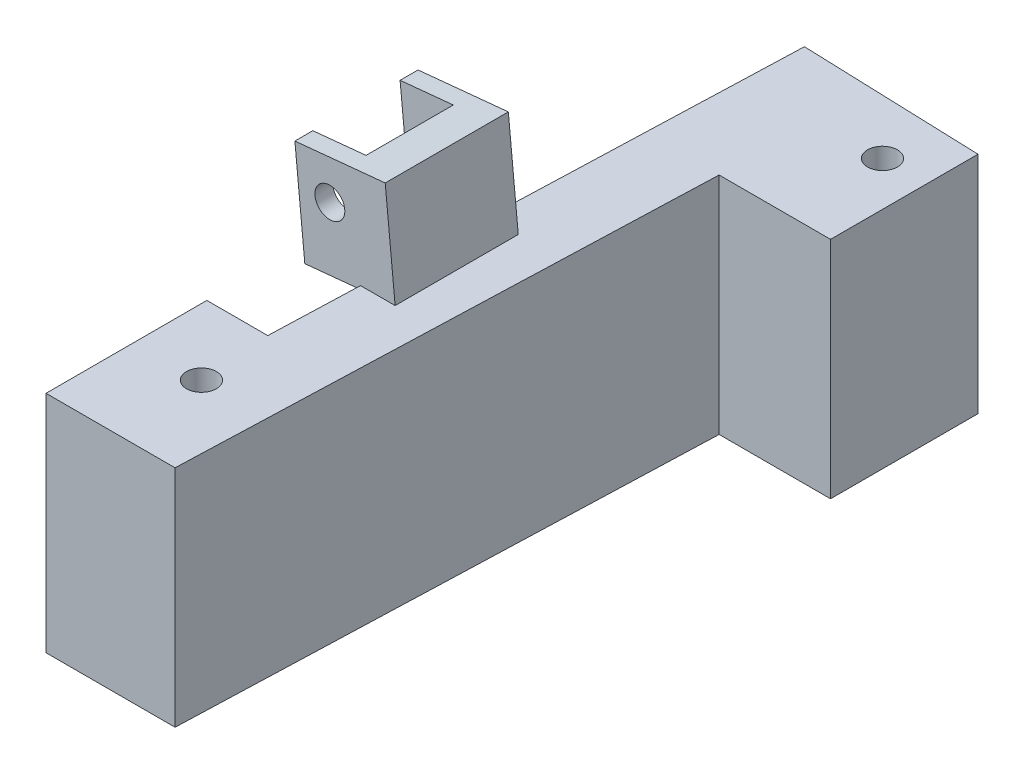
SolidWorks part; units mm, degrees
ref_plane "Front Plane" through (0, 0, 0) normal (0, 0, 1) x (1, 0, 0)
ref_plane "Top Plane" through (0, 0, 0) normal (0, 1, 0) x (1, 0, 0)
ref_plane "Right Plane" through (0, 0, 0) normal (1, 0, 0) x (0, 0, -1)
sketch "Sketch1" plane through (0, 0, 0) normal (0, 0, 1) x (1, 0, 0)
  line L0 (476.9237, 158.5913) -> (479.0335, 137.0791)
  line L1 (479.0335, 137.0791) -> (498.2247, 138.9613)
  line L2 (498.2247, 138.9613) -> (496.115, 160.4735)
  line L3 (496.115, 160.4735) -> (476.9237, 158.5913)
  line L4 (485.2846, 141.5205) -> (469.8952, 140.0112) construction
  line L5 (485.2846, 141.5205) -> (469.8952, 140.0112)
  arc A0 (489.9044, 158.7414) -> (483.4252, 160.4795) centre (484.3549, 151) ccw construction
  arc A1 (491.3026, 144.4842) -> (489.9044, 158.7414) centre (484.3549, 151) ccw construction
  arc A2 (485.2846, 141.5205) -> (491.3026, 144.4842) centre (484.3549, 151) ccw construction
  arc A3 (489.9044, 158.7414) -> (483.4252, 160.4795) centre (484.3549, 151) ccw
  arc A4 (491.3026, 144.4842) -> (489.9044, 158.7414) centre (484.3549, 151) ccw
  arc A5 (485.2846, 141.5205) -> (491.3026, 144.4842) centre (484.3549, 151) ccw
  dimension "D1" = 6.35
  dimension "D2" = 3.81
extrude "Boss-Extrude5" add sketch "Sketch1" against normal blind 22.352 contours A5 L5 L0 L1 L2 L3 A3 A4 region at (482.0029, 140.8922, 0)
sketch "Sketch2" plane through (0, 0, -22.352) normal (0, 0, -1) x (-1, 0, 0)
  line L0 (-488.2317, 159.7003) -> (-476.9237, 158.5913)
  line L1 (-476.9237, 158.5913) -> (-478.6616, 140.8709)
  line L2 (-478.6616, 140.8709) -> (-485.2846, 141.5205)
  arc A0 (-485.2846, 141.5205) -> (-488.2317, 159.7003) centre (-484.3549, 151) cw
  circle A1 centre (-484.3549, 151) radius 3.175 construction
  circle A2 centre (-484.3549, 151) radius 3.175
  circle A3 centre (-484.3549, 151) radius 3.175
  arc M5 (-485.2846, 141.5205) -> (-488.2317, 159.7003) centre (-484.3549, 151) cw
  line M10 (-478.6616, 140.8709) -> (-485.2846, 141.5205)
extrude "Boss-Extrude7" add sketch "Sketch2" against normal blind 3.81 contours L1 L0 A2 M5 M10 region at (482.6025, 158.8937, -22.352)
sketch "Sketch3" plane through (0, 0, 0) normal (0, 0, 1) x (1, 0, 0)
  line L0 (476.9237, 158.5913) -> (479.0335, 137.0791)
  line L1 (479.0335, 137.0791) -> (498.2247, 138.9613)
  line L2 (498.2247, 138.9613) -> (496.115, 160.4735)
  line L3 (496.115, 160.4735) -> (476.9237, 158.5913)
  circle A0 centre (484.3549, 151) radius 3.175 construction
  circle A1 centre (484.3549, 151) radius 3.175
  circle A2 centre (484.3549, 151) radius 3.175
  arc M6 (488.2317, 159.7003) -> (485.2846, 141.5205) centre (484.3549, 151) cw
  line M7 (485.2846, 141.5205) -> (478.6616, 140.8709)
  line M8 (478.6616, 140.8709) -> (479.0335, 137.0791)
  line M9 (479.0335, 137.0791) -> (498.2247, 138.9613)
  line M10 (498.2247, 138.9613) -> (496.115, 160.4735)
  line M11 (496.115, 160.4735) -> (488.2317, 159.7003)
extrude "Boss-Extrude8" add sketch "Sketch3" along normal blind 3.81 contours L3 L0 A1 M6 M7 | M11 M6 M7 M8 M9 M10 region at (482.6025, 158.8937, 0) region at (482.0029, 140.8922, 0)
ref_plane "Plane1" through (0, 138.9613, 0) normal (0, 1, 0) x (1, 0, 0)
sketch "Sketch4" plane through (0, 138.9613, 0) normal (0, 1, 0) x (1, 0, 0)
  line L0 (494.0725, 87.3113) -> (532.2914, 85.9701)
  line L2 (494.0725, 87.3113) -> (490.2062, -22.86)
  line L4 (508.6117, 54.6403) -> (504.6925, -57.0385)
  line L5 (532.2914, 85.9701) -> (532.2914, 54.6403)
  line L6 (532.2914, 54.6403) -> (508.6117, 54.6403)
  line L7 (504.6925, -57.0385) -> (477.2694, -57.0385)
  line L8 (477.2694, -57.0385) -> (477.2694, -22.86)
  line L9 (477.2694, -22.86) -> (490.2062, -22.86)
  dimension "D1" = 90
  dimension "D2" = 111.7476
  dimension "D3" = 180
  dimension "D4" = 110.1713
extrude "Boss-Extrude9" add sketch "Sketch4" against normal up to surface (47.7499 mm away)
sketch "Sketch6" plane through (0, 138.9613, 0) normal (0, 1, 0) x (1, 0, 0)
  circle A0 centre (491.3661, -38.1051) radius 3.175
  circle A1 centre (522.9171, 75.0492) radius 3.175
  dimension "D1" = 6.35
  dimension "D2" = 6.35
extrude "Cut-Extrude1" cut sketch "Sketch6" against normal blind 6.35
